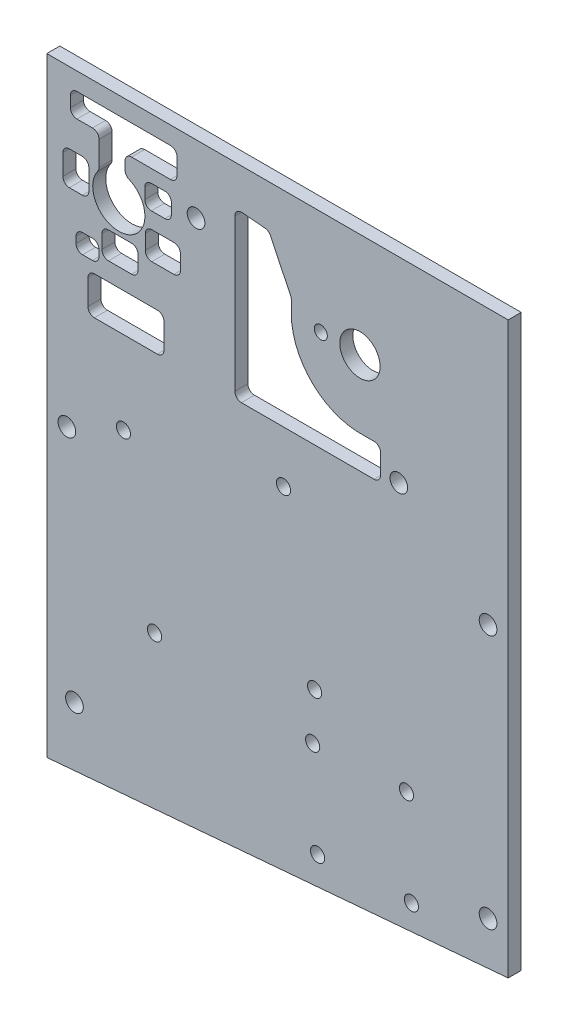
SolidWorks part; units mm, degrees
material "Acrylic (Medium-high impact)"
ref_plane "Front Plane" through (0, 0, 0) normal (0, 0, 1) x (1, 0, 0)
ref_plane "Top Plane" through (0, 0, 0) normal (0, 1, 0) x (1, 0, 0)
ref_plane "Right Plane" through (0, 0, 0) normal (1, 0, 0) x (0, 0, -1)
sketch "Sketch1" plane through (0, 0, 0) normal (0, 0, 1) x (1, 0, 0)
  line L4 (112.268, 0) -> (0, 0)
  line L5 (0, 0) -> (0, -148.336)
  line L6 (0, -148.336) -> (112.268, -138.684)
  line L7 (112.268, -138.684) -> (112.268, 0)
  line L8 (112.268, 0) -> (0, 0)
  line L9 (0, 0) -> (0, -148.336)
  line L10 (0, -148.336) -> (112.268, -138.684)
  line L11 (112.268, -138.684) -> (112.268, 0)
  dimension "D1" = 0
extrude "Boss-Extrude1" add sketch "Sketch1" against normal blind 3.175
hole_wizard "#6 Clearance Hole1" positions "Sketch3" profile "Sketch2" hole size "#6" standard "ANSI Inch" end condition through all
sketch "Sketch3" plane through (0, 0, 0) normal (0, 0, 1) x (1, 0, 0)
  point P0 (6.731, -133.35)
  point P3 (107.3785, -128.5875)
  point P6 (107.3785, -66.675)
  point P9 (4.8895, -76.2)
sketch "Sketch2" plane through (6.731, -133.35, 0) normal (1, 0, 0) x (0, -1, 0)
  line L0 (0, 0) -> (0, 3.175)
  line L1 (0, 3.175) -> (2.1526, 3.175)
  line L2 (2.1526, 3.175) -> (2.1526, 0)
  line L5 (2.1526, 0) -> (0, 0)
  line L11 (0, -6.35) -> (0, 107.95) construction
  dimension "Thru Hole Dia." = 4.3053
  dimension "Thru Hole Depth" = 3.175
hole_wizard "#4 Clearance Hole1" positions "Sketch5" profile "Sketch4" hole size "#4" standard "ANSI Inch" end condition through all
sketch "Sketch5" plane through (0, 0, 0) normal (0, 0, 1) x (1, 0, 0)
  point P0 (18.6445, -70.0322)
  point P3 (57.6028, -62.4595)
  point P6 (65.1755, -101.4178)
  point P9 (26.2172, -108.9905)
  point P12 (65.8919, -135.8375)
  point P15 (88.7205, -134.6411)
  point P18 (87.5241, -111.8125)
  point P21 (64.6955, -113.0089)
sketch "Sketch4" plane through (18.6445, -70.0322, 0) normal (1, 0, 0) x (0, -1, 0)
  line L0 (0, 0) -> (0, 3.175)
  line L1 (0, 3.175) -> (1.7272, 3.175)
  line L2 (1.7272, 3.175) -> (1.7272, 0)
  line L5 (1.7272, 0) -> (0, 0)
  line L11 (0, -6.35) -> (0, 107.95) construction
  dimension "Thru Hole Dia." = 3.4544
  dimension "Thru Hole Depth" = 3.175
hole_wizard "#6 Clearance Hole2" positions "Sketch7" profile "Sketch6" hole size "#6" standard "ANSI Inch" end condition through all
sketch "Sketch7" plane through (0, 0, 0) normal (0, 0, 1) x (1, 0, 0)
  point P0 (36.322, -16.51)
  point P3 (85.6615, -47.625)
sketch "Sketch6" plane through (36.322, -16.51, 0) normal (1, 0, 0) x (0, -1, 0)
  line L0 (0, 0) -> (0, 3.175)
  line L1 (0, 3.175) -> (2.1526, 3.175)
  line L2 (2.1526, 3.175) -> (2.1526, 0)
  line L5 (2.1526, 0) -> (0, 0)
  line L11 (0, -6.35) -> (0, 107.95) construction
  dimension "Thru Hole Dia." = 4.3053
  dimension "Thru Hole Depth" = 3.175
hole_wizard "3/8 (0.386) Diameter Hole1" positions "Sketch11" profile "Sketch10" hole size "3/8" standard "ANSI Inch" end condition through all
sketch "Sketch11" plane through (0, 0, 0) normal (0, 0, 1) x (1, 0, 0)
  point P0 (76.2, -25.4)
sketch "Sketch10" plane through (76.2, -25.4, 0) normal (1, 0, 0) x (0, -1, 0)
  line L0 (0, 0) -> (0, 3.175)
  line L1 (0, 3.175) -> (4.9022, 3.175)
  line L2 (4.9022, 3.175) -> (4.9022, 0)
  line L5 (4.9022, 0) -> (0, 0)
  line L11 (0, -6.35) -> (0, 107.95) construction
  dimension "Thru Hole Dia." = 9.8044
  dimension "Thru Hole Depth" = 3.175
hole_wizard "1/8 (0.125) Diameter Hole1" positions "Sketch16" profile "Sketch17" hole size "1/8" standard "ANSI Inch" end condition through all
sketch "Sketch16" plane through (0, 0, 0) normal (0, 0, 1) x (1, 0, 0)
  line L0 (66.675, -25.4) -> (76.2, -25.4) construction
  line L1 (76.2, -25.4) -> (76.2, 0) construction
  line L2 (112.268, 0) -> (0, 0) construction
  point P0 (66.675, -25.4)
  dimension "D1" = 9.525
  dimension "D2" = 90
sketch "Sketch17" plane through (66.675, -25.4, 0) normal (1, 0, 0) x (0, -1, 0)
  line L0 (0, 0) -> (0, 3.175)
  line L1 (0, 3.175) -> (1.5875, 3.175)
  line L2 (1.5875, 3.175) -> (1.5875, 0)
  line L5 (1.5875, 0) -> (0, 0)
  line L11 (0, -6.35) -> (0, 107.95) construction
  dimension "Thru Hole Dia." = 3.175
  dimension "Thru Hole Depth" = 3.175
hole_wizard "1/2 (0.5) Diameter Hole1" positions "Sketch13" profile "Sketch12" hole size "1/2" standard "ANSI Inch" end condition through all
sketch "Sketch13" plane through (0, 0, 0) normal (0, 0, 1) x (1, 0, 0)
  point P0 (17.526, -22.352)
sketch "Sketch12" plane through (17.526, -22.352, 0) normal (1, 0, 0) x (0, -1, 0)
  line L0 (0, 0) -> (0, 3.175)
  line L1 (0, 3.175) -> (6.35, 3.175)
  line L2 (6.35, 3.175) -> (6.35, 0)
  line L5 (6.35, 0) -> (0, 0)
  line L11 (0, -6.35) -> (0, 107.95) construction
  dimension "Thru Hole Dia." = 12.7
  dimension "Thru Hole Depth" = 3.175
sketch "Sketch15" plane through (0, 0, 0) normal (0, 0, 1) x (1, 0, 0)
  line L0 (7.3391, -4.3284) -> (30.0964, -4.3284)
  line L1 (31.6839, -5.9159) -> (31.6839, -9.9082)
  line L2 (30.0964, -11.4957) -> (20.631, -11.4957)
  line L3 (19.0435, -13.0832) -> (19.0435, -18.5245)
  line L4 (17.456, -20.112) -> (14.3108, -20.112)
  line L5 (12.7233, -18.5245) -> (12.7233, -11.7148)
  line L6 (11.1358, -10.1273) -> (7.3391, -10.1273)
  line L7 (5.7516, -8.5398) -> (5.7516, -5.9159)
  line L8 (45.7668, -11.3344) -> (45.7668, -48.3053)
  line L20 (59.3363, -21.3703) -> (54.4079, -11.1365)
  line L21 (53.1157, -10.2438) -> (47.4924, -9.7529)
  line L22 (25.4335, -14.6362) -> (28.7265, -14.6362)
  line L23 (30.314, -16.2237) -> (30.314, -18.8368)
  line L24 (28.7265, -20.4243) -> (25.4335, -20.4243)
  line L25 (23.846, -18.8368) -> (23.846, -16.2237)
  line L26 (25.5483, -24.3452) -> (30.932, -24.3452)
  line L27 (32.5195, -25.9327) -> (32.5195, -29.489)
  line L28 (30.932, -31.0765) -> (25.5483, -31.0765)
  line L29 (23.9608, -29.489) -> (23.9608, -25.9327)
  line L30 (14.9979, -29.6607) -> (20.6331, -29.6607)
  line L31 (22.2206, -31.2482) -> (22.2206, -34.595)
  line L32 (20.6331, -36.1825) -> (14.9979, -36.1825)
  line L33 (13.4104, -34.595) -> (13.4104, -31.2482)
  line L34 (5.5045, -17.3366) -> (8.6394, -17.3366)
  line L35 (10.2269, -18.9241) -> (10.2269, -23.937)
  line L36 (8.6394, -25.5245) -> (5.5045, -25.5245)
  line L37 (3.917, -23.937) -> (3.917, -18.9241)
  line L38 (8.6994, -33.3754) -> (11.1093, -33.3754)
  line L39 (12.6968, -34.9629) -> (12.6968, -36.4594)
  line L40 (11.1093, -38.0469) -> (8.6994, -38.0469)
  line L41 (7.1119, -36.4594) -> (7.1119, -34.9629)
  line L42 (11.5858, -40.6238) -> (26.9166, -40.6238)
  line L43 (28.5041, -42.2113) -> (28.5041, -48.3053)
  line L44 (26.9166, -49.8928) -> (11.5858, -49.8928)
  line L45 (9.9983, -48.3053) -> (9.9983, -42.2113)
  line L46 (81.2243, -43.4934) -> (81.2243, -48.3053)
  line L47 (75.5632, -41.9059) -> (79.6368, -41.9059)
  line L48 (59.4935, -22.0591) -> (59.4935, -25.0385)
  line L49 (79.6368, -49.8928) -> (47.3543, -49.8928)
  arc A11 (45.7668, -11.3344) -> (47.4924, -9.7529) centre (47.3543, -11.3344) cw
  arc A12 (54.4079, -11.1365) -> (53.1157, -10.2438) centre (52.9777, -11.8253) ccw
  arc A13 (28.7265, -14.6362) -> (30.314, -16.2237) centre (28.7265, -16.2237) cw
  arc A14 (30.314, -18.8368) -> (28.7265, -20.4243) centre (28.7265, -18.8368) cw
  arc A15 (25.4335, -20.4243) -> (23.846, -18.8368) centre (25.4335, -18.8368) cw
  arc A16 (25.4335, -14.6362) -> (23.846, -16.2237) centre (25.4335, -16.2237) ccw
  arc A17 (30.932, -24.3452) -> (32.5195, -25.9327) centre (30.932, -25.9327) cw
  arc A18 (32.5195, -29.489) -> (30.932, -31.0765) centre (30.932, -29.489) cw
  arc A19 (25.5483, -31.0765) -> (23.9608, -29.489) centre (25.5483, -29.489) cw
  arc A20 (25.5483, -24.3452) -> (23.9608, -25.9327) centre (25.5483, -25.9327) ccw
  arc A21 (20.6331, -29.6607) -> (22.2206, -31.2482) centre (20.6331, -31.2482) cw
  arc A22 (22.2206, -34.595) -> (20.6331, -36.1825) centre (20.6331, -34.595) cw
  arc A23 (14.9979, -36.1825) -> (13.4104, -34.595) centre (14.9979, -34.595) cw
  arc A24 (14.9979, -29.6607) -> (13.4104, -31.2482) centre (14.9979, -31.2482) ccw
  arc A25 (8.6394, -17.3366) -> (10.2269, -18.9241) centre (8.6394, -18.9241) cw
  arc A26 (10.2269, -23.937) -> (8.6394, -25.5245) centre (8.6394, -23.937) cw
  arc A27 (5.5045, -25.5245) -> (3.917, -23.937) centre (5.5045, -23.937) cw
  arc A28 (5.5045, -17.3366) -> (3.917, -18.9241) centre (5.5045, -18.9241) ccw
  arc A29 (11.1093, -33.3754) -> (12.6968, -34.9629) centre (11.1093, -34.9629) cw
  arc A30 (12.6968, -36.4594) -> (11.1093, -38.0469) centre (11.1093, -36.4594) cw
  arc A31 (8.6994, -38.0469) -> (7.1119, -36.4594) centre (8.6994, -36.4594) cw
  arc A32 (8.6994, -33.3754) -> (7.1119, -34.9629) centre (8.6994, -34.9629) ccw
  arc A33 (26.9166, -40.6238) -> (28.5041, -42.2113) centre (26.9166, -42.2113) cw
  arc A34 (28.5041, -48.3053) -> (26.9166, -49.8928) centre (26.9166, -48.3053) cw
  arc A35 (11.5858, -49.8928) -> (9.9983, -48.3053) centre (11.5858, -48.3053) cw
  arc A36 (11.5858, -40.6238) -> (9.9983, -42.2113) centre (11.5858, -42.2113) ccw
  arc A37 (30.0964, -4.3284) -> (31.6839, -5.9159) centre (30.0964, -5.9159) cw
  arc A38 (7.3391, -4.3284) -> (5.7516, -5.9159) centre (7.3391, -5.9159) ccw
  arc A39 (7.3391, -10.1273) -> (5.7516, -8.5398) centre (7.3391, -8.5398) cw
  arc A40 (31.6839, -9.9082) -> (30.0964, -11.4957) centre (30.0964, -9.9082) cw
  arc A41 (12.7233, -11.7148) -> (11.1358, -10.1273) centre (11.1358, -11.7148) ccw
  arc A42 (20.631, -11.4957) -> (19.0435, -13.0832) centre (20.631, -13.0832) ccw
  arc A43 (19.0435, -18.5245) -> (17.456, -20.112) centre (17.456, -18.5245) cw
  arc A44 (14.3108, -20.112) -> (12.7233, -18.5245) centre (14.3108, -18.5245) cw
  arc A45 (59.4935, -25.0385) -> (75.5632, -41.9059) centre (76.3806, -25.0385) ccw
  arc A46 (47.3543, -49.8928) -> (45.7668, -48.3053) centre (47.3543, -48.3053) cw
  arc A47 (81.2243, -48.3053) -> (79.6368, -49.8928) centre (79.6368, -48.3053) cw
  arc A48 (81.2243, -43.4934) -> (79.6368, -41.9059) centre (79.6368, -43.4934) ccw
  arc A49 (59.3363, -21.3703) -> (59.4935, -22.0591) centre (57.906, -22.0591) cw
  point P14 (46.0085, -49.8928)
  dimension "D1" = 1.5875
  dimension "D2" = 1.5875
  dimension "D3" = 1.5875
  dimension "D4" = 1.5875
  dimension "D5" = 1.5875
  dimension "D6" = 1.5875
extrude "Backlighting LED Holes" cut sketch "Sketch15" against normal through all
fillet "Thin Section Fillet" radius 1.5875 2 edges at (19.0435, -16.186, -1.5875) (12.7233, -18.1979, -1.5875)
